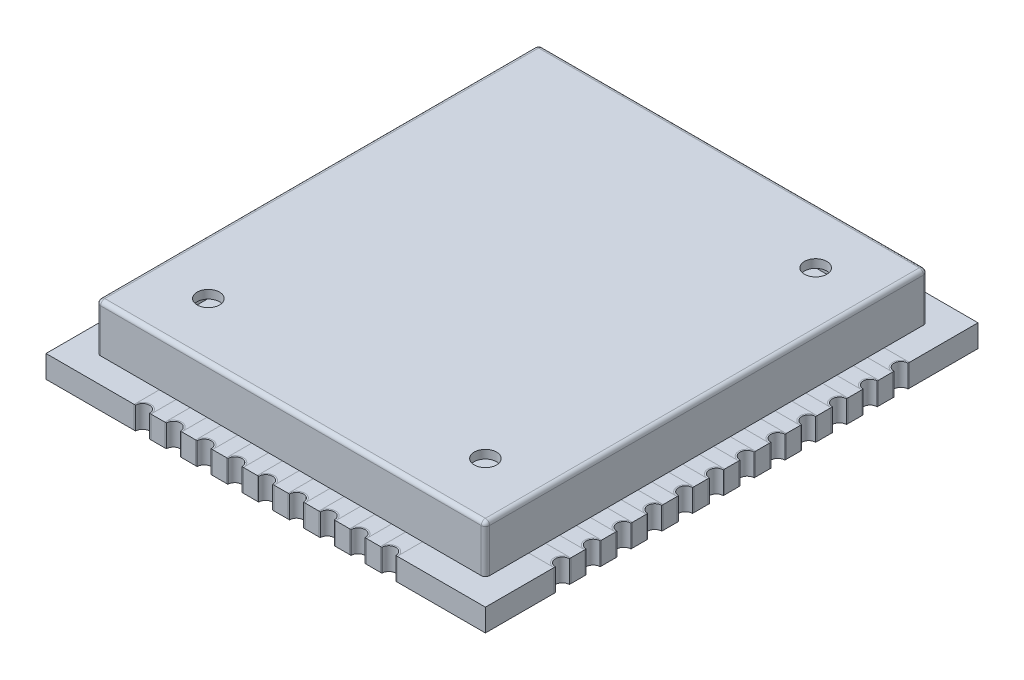
SolidWorks part; units mm, degrees
note: The reader was unsure of these and kept them because the rebuilt part matched: shared geometry of "Sketch5<2>", "Sketch5<3>", "Sketch5<4>", "Sketch3<2>".
other "Shield"
other "PCB"
ref_plane "Front Plane" through (0, 0, 0) normal (0, 0, 1) x (1, 0, 0)
ref_plane "Top Plane" through (0, 0, 0) normal (0, 1, 0) x (1, 0, 0)
ref_plane "Right Plane" through (0, 0, 0) normal (1, 0, 0) x (0, 0, -1)
sketch "Sketch1" plane through (0, 0, 0) normal (0, 1, 0) x (1, 0, 0)
  line L1 (-7.85, -8.8) -> (7.85, -8.8)
  line L2 (-7.85, -8.8) -> (-7.85, 8.8)
  line L3 (-7.85, 8.8) -> (7.85, 8.8)
  line L4 (7.85, -8.8) -> (7.85, 8.8)
  line L5 (-7.85, -8.8) -> (7.85, 8.8) construction
  line L6 (-7.85, 8.8) -> (7.85, -8.8) construction
  point P0 (0, 0)
  dimension "D1" = 17.6
  dimension "D2" = 15.7
extrude "PCB BASE" add sketch "Sketch1" along normal blind 0.8
sketch "Sketch2" plane through (0, 0, 0) normal (0, 1, 0) x (1, 0, 0)
  line L1 (-6.95, -7.9) -> (6.95, -7.9)
  line L2 (-6.95, -7.9) -> (-6.95, 7.9)
  line L3 (-6.95, 7.9) -> (6.95, 7.9)
  line L4 (6.95, -7.9) -> (6.95, 7.9)
  line L5 (-6.95, -7.9) -> (6.95, 7.9) construction
  line L6 (-6.95, 7.9) -> (6.95, -7.9) construction
  point P0 (0, 0)
  dimension "D1" = 15.8
  dimension "D2" = 13.9
extrude "SHIELD" add sketch "Sketch2" along normal blind 1.7 from surface at 0.8 separate body starting at face at (0, 0.8, 0)
shell "Shield shelling" thickness 0.3
sketch "Sketch4" plane through (0, 0, 0) normal (0, 1, 0) x (1, 0, 0)
  line L0 (-6.95, 7.9) -> (-6.95, -7.9) construction
  line L1 (-6.95, -7.9) -> (6.95, -7.9) construction
  line L2 (6.95, -7.9) -> (6.95, 7.9) construction
  line L3 (6.95, 7.9) -> (-6.95, 7.9) construction
  circle A0 centre (-4.95, -5.9) radius 0.4
  circle A1 centre (4.95, 5.9) radius 0.4
  circle A2 centre (4.95, -5.9) radius 0.4
  dimension "D1" = 0.8
  dimension "D2" = 0.8
  dimension "D3" = 0.8
  dimension "D4" = 2
  dimension "D5" = 2
  dimension "D6" = 2
  dimension "D7" = 2
extrude "Holes in shield" cut sketch "Sketch4" against normal up to next from surface
sketch "Sketch3" plane through (0, 0, 0) normal (0, 1, 0) x (1, 0, 0)
  line L0 (-7.85, 8.8) -> (-7.85, -8.8) construction
  line L1 (-7.85, -8.8) -> (7.85, -8.8) construction
  line L2 (-7.85, -5.75) -> (-7.85, -6.35)
  line L3 (-7.85, -4.65) -> (-7.85, -5.25)
  line L4 (-7.85, -3.55) -> (-7.85, -4.15)
  line L5 (-7.85, -2.45) -> (-7.85, -3.05)
  line L6 (-7.85, -1.35) -> (-7.85, -1.95)
  line L7 (-7.85, -0.25) -> (-7.85, -0.85)
  line L8 (-7.85, 0.85) -> (-7.85, 0.25)
  line L9 (-7.85, 1.95) -> (-7.85, 1.35)
  line L10 (-7.85, 3.05) -> (-7.85, 2.45)
  line L11 (-7.85, 4.15) -> (-7.85, 3.55)
  line L12 (-7.85, 5.25) -> (-7.85, 4.65)
  line L13 (-7.85, 6.35) -> (-7.85, 5.75)
  line L14 (0, 8.8) -> (0, -8.8) construction
  line L15 (7.85, 8.8) -> (-7.85, 8.8) construction
  line L16 (7.85, 6.35) -> (7.85, 5.75)
  line L17 (7.85, 5.25) -> (7.85, 4.65)
  line L18 (7.85, 4.15) -> (7.85, 3.55)
  line L19 (7.85, 3.05) -> (7.85, 2.45)
  line L20 (7.85, 1.95) -> (7.85, 1.35)
  line L21 (7.85, 0.85) -> (7.85, 0.25)
  line L22 (7.85, -0.25) -> (7.85, -0.85)
  line L23 (7.85, -1.35) -> (7.85, -1.95)
  line L24 (7.85, -2.45) -> (7.85, -3.05)
  line L25 (7.85, -3.55) -> (7.85, -4.15)
  line L26 (7.85, -4.65) -> (7.85, -5.25)
  line L27 (7.85, -5.75) -> (7.85, -6.35)
  line L28 (-4.7, -8.8) -> (-4.1, -8.8)
  line L29 (-3.6, -8.8) -> (-3, -8.8)
  line L30 (-2.5, -8.8) -> (-1.9, -8.8)
  line L31 (-1.4, -8.8) -> (-0.8, -8.8)
  line L32 (-0.3, -8.8) -> (0.3, -8.8)
  line L33 (0.8, -8.8) -> (1.4, -8.8)
  line L34 (1.9, -8.8) -> (2.5, -8.8)
  line L35 (3, -8.8) -> (3.6, -8.8)
  line L36 (4.1, -8.8) -> (4.7, -8.8)
  line L37 (-7.85, 0) -> (7.85, 0) construction
  line L38 (7.85, -8.8) -> (7.85, 8.8) construction
  line L39 (4.1, 8.8) -> (4.7, 8.8)
  line L40 (3, 8.8) -> (3.6, 8.8)
  line L41 (1.9, 8.8) -> (2.5, 8.8)
  line L42 (0.8, 8.8) -> (1.4, 8.8)
  line L43 (-0.3, 8.8) -> (0.3, 8.8)
  line L44 (-1.4, 8.8) -> (-0.8, 8.8)
  line L45 (-2.5, 8.8) -> (-1.9, 8.8)
  line L46 (-3.6, 8.8) -> (-3, 8.8)
  line L47 (-4.7, 8.8) -> (-4.1, 8.8)
  arc A0 (-7.85, -5.75) -> (-7.85, -6.35) centre (-7.85, -6.05) cw
  arc A1 (-7.85, -4.65) -> (-7.85, -5.25) centre (-7.85, -4.95) cw
  arc A2 (-7.85, -3.55) -> (-7.85, -4.15) centre (-7.85, -3.85) cw
  arc A3 (-7.85, -2.45) -> (-7.85, -3.05) centre (-7.85, -2.75) cw
  arc A4 (-7.85, -1.35) -> (-7.85, -1.95) centre (-7.85, -1.65) cw
  arc A5 (-7.85, -0.25) -> (-7.85, -0.85) centre (-7.85, -0.55) cw
  arc A6 (-7.85, 0.85) -> (-7.85, 0.25) centre (-7.85, 0.55) cw
  arc A7 (-7.85, 1.95) -> (-7.85, 1.35) centre (-7.85, 1.65) cw
  arc A8 (-7.85, 3.05) -> (-7.85, 2.45) centre (-7.85, 2.75) cw
  arc A9 (-7.85, 4.15) -> (-7.85, 3.55) centre (-7.85, 3.85) cw
  arc A10 (-7.85, 5.25) -> (-7.85, 4.65) centre (-7.85, 4.95) cw
  arc A11 (-7.85, 6.35) -> (-7.85, 5.75) centre (-7.85, 6.05) cw
  arc A12 (7.85, 6.35) -> (7.85, 5.75) centre (7.85, 6.05) ccw
  arc A13 (7.85, 5.25) -> (7.85, 4.65) centre (7.85, 4.95) ccw
  arc A14 (7.85, 4.15) -> (7.85, 3.55) centre (7.85, 3.85) ccw
  arc A15 (7.85, 3.05) -> (7.85, 2.45) centre (7.85, 2.75) ccw
  arc A16 (7.85, 1.95) -> (7.85, 1.35) centre (7.85, 1.65) ccw
  arc A17 (7.85, 0.85) -> (7.85, 0.25) centre (7.85, 0.55) ccw
  arc A18 (7.85, -0.25) -> (7.85, -0.85) centre (7.85, -0.55) ccw
  arc A19 (7.85, -1.35) -> (7.85, -1.95) centre (7.85, -1.65) ccw
  arc A20 (7.85, -2.45) -> (7.85, -3.05) centre (7.85, -2.75) ccw
  arc A21 (7.85, -3.55) -> (7.85, -4.15) centre (7.85, -3.85) ccw
  arc A22 (7.85, -4.65) -> (7.85, -5.25) centre (7.85, -4.95) ccw
  arc A23 (7.85, -5.75) -> (7.85, -6.35) centre (7.85, -6.05) ccw
  arc A24 (-4.7, -8.8) -> (-4.1, -8.8) centre (-4.4, -8.8) cw
  arc A25 (-3.6, -8.8) -> (-3, -8.8) centre (-3.3, -8.8) cw
  arc A26 (-2.5, -8.8) -> (-1.9, -8.8) centre (-2.2, -8.8) cw
  arc A27 (-1.4, -8.8) -> (-0.8, -8.8) centre (-1.1, -8.8) cw
  arc A28 (-0.3, -8.8) -> (0.3, -8.8) centre (0, -8.8) cw
  arc A29 (0.8, -8.8) -> (1.4, -8.8) centre (1.1, -8.8) cw
  arc A30 (1.9, -8.8) -> (2.5, -8.8) centre (2.2, -8.8) cw
  arc A31 (3, -8.8) -> (3.6, -8.8) centre (3.3, -8.8) cw
  arc A32 (4.1, -8.8) -> (4.7, -8.8) centre (4.4, -8.8) cw
  arc A33 (4.1, 8.8) -> (4.7, 8.8) centre (4.4, 8.8) ccw
  arc A34 (3, 8.8) -> (3.6, 8.8) centre (3.3, 8.8) ccw
  arc A35 (1.9, 8.8) -> (2.5, 8.8) centre (2.2, 8.8) ccw
  arc A36 (0.8, 8.8) -> (1.4, 8.8) centre (1.1, 8.8) ccw
  arc A37 (-0.3, 8.8) -> (0.3, 8.8) centre (0, 8.8) ccw
  arc A38 (-1.4, 8.8) -> (-0.8, 8.8) centre (-1.1, 8.8) ccw
  arc A39 (-2.5, 8.8) -> (-1.9, 8.8) centre (-2.2, 8.8) ccw
  arc A40 (-3.6, 8.8) -> (-3, 8.8) centre (-3.3, 8.8) ccw
  arc A41 (-4.7, 8.8) -> (-4.1, 8.8) centre (-4.4, 8.8) ccw
  point P0 (-7.85, -6.05)
  dimension "D2" = 0.3
  dimension "D4" = 0.3
  dimension "D1" = 2.75
  dimension "D5" = 3.45
  dimension "D3" = 12
  dimension "D6" = 9
extrude "Cut-Extrude1" cut sketch "Sketch3" against normal through all and the other way through all
sketch "Sketch5" plane through (0, 0, 0) normal (0, 1, 0) x (1, 0, 0)
  line L0 (-7.85, -4.65) -> (-6.85, -4.65)
  line L1 (-7.85, -5.75) -> (-6.85, -5.75)
  line L2 (-7.85, -5.75) -> (-7.85, -6.35)
  line L3 (-7.85, -6.35) -> (-6.85, -6.35)
  line L4 (-6.85, -5.75) -> (-6.85, -6.35)
  line L5 (-7.85, -4.65) -> (-7.85, -5.25)
  line L6 (-7.85, -5.25) -> (-6.85, -5.25)
  line L7 (-6.85, -4.65) -> (-6.85, -5.25)
  line L8 (-7.85, -3.55) -> (-6.85, -3.55)
  line L9 (-7.85, -3.55) -> (-7.85, -4.15)
  line L10 (-7.85, -4.15) -> (-6.85, -4.15)
  line L11 (-6.85, -3.55) -> (-6.85, -4.15)
  line L12 (-7.85, -2.45) -> (-6.85, -2.45)
  line L13 (-7.85, -2.45) -> (-7.85, -3.05)
  line L14 (-7.85, -3.05) -> (-6.85, -3.05)
  line L15 (-6.85, -2.45) -> (-6.85, -3.05)
  line L16 (-7.85, -1.35) -> (-6.85, -1.35)
  line L17 (-7.85, -1.35) -> (-7.85, -1.95)
  line L18 (-7.85, -1.95) -> (-6.85, -1.95)
  line L19 (-6.85, -1.35) -> (-6.85, -1.95)
  line L20 (-7.85, -0.25) -> (-6.85, -0.25)
  line L21 (-7.85, -0.25) -> (-7.85, -0.85)
  line L22 (-7.85, -0.85) -> (-6.85, -0.85)
  line L23 (-6.85, -0.25) -> (-6.85, -0.85)
  line L24 (-7.85, 0.85) -> (-6.85, 0.85)
  line L25 (-7.85, 0.85) -> (-7.85, 0.25)
  line L26 (-7.85, 0.25) -> (-6.85, 0.25)
  line L27 (-6.85, 0.85) -> (-6.85, 0.25)
  line L28 (-7.85, 1.95) -> (-6.85, 1.95)
  line L29 (-7.85, 1.95) -> (-7.85, 1.35)
  line L30 (-7.85, 1.35) -> (-6.85, 1.35)
  line L31 (-6.85, 1.95) -> (-6.85, 1.35)
  line L32 (-7.85, 3.05) -> (-6.85, 3.05)
  line L33 (-7.85, 3.05) -> (-7.85, 2.45)
  line L34 (-7.85, 2.45) -> (-6.85, 2.45)
  line L35 (-6.85, 3.05) -> (-6.85, 2.45)
  line L36 (-7.85, 4.15) -> (-6.85, 4.15)
  line L37 (-7.85, 4.15) -> (-7.85, 3.55)
  line L38 (-7.85, 3.55) -> (-6.85, 3.55)
  line L39 (-6.85, 4.15) -> (-6.85, 3.55)
  line L40 (-7.85, 5.25) -> (-6.85, 5.25)
  line L41 (-7.85, 5.25) -> (-7.85, 4.65)
  line L42 (-7.85, 4.65) -> (-6.85, 4.65)
  line L43 (-6.85, 5.25) -> (-6.85, 4.65)
  line L44 (-7.85, 6.35) -> (-6.85, 6.35)
  line L45 (-7.85, 6.35) -> (-7.85, 5.75)
  line L46 (-7.85, 5.75) -> (-6.85, 5.75)
  line L47 (-6.85, 6.35) -> (-6.85, 5.75)
  line L48 (-7.85, 0) -> (7.85, 0) construction
  line L49 (-7.85, 0.25) -> (-7.85, -0.25) construction
  line L50 (7.85, -0.25) -> (7.85, 0.25) construction
  line L51 (0, 8.5) -> (0, -8.5) construction
  line L52 (7.85, 5.25) -> (6.85, 5.25) [skipped]
  line L53 (7.85, 6.35) -> (6.85, 6.35)
  line L54 (7.85, 6.35) -> (7.85, 5.75)
  line L55 (7.85, 5.75) -> (6.85, 5.75)
  line L56 (6.85, 6.35) -> (6.85, 5.75)
  line L57 (7.85, 5.25) -> (7.85, 4.65) [skipped]
  line L58 (7.85, 4.65) -> (6.85, 4.65) [skipped]
  line L59 (6.85, 5.25) -> (6.85, 4.65) [skipped]
  line L60 (7.85, 4.15) -> (6.85, 4.15)
  line L61 (7.85, 4.15) -> (7.85, 3.55)
  line L62 (7.85, 3.55) -> (6.85, 3.55)
  line L63 (6.85, 4.15) -> (6.85, 3.55)
  line L64 (7.85, 3.05) -> (6.85, 3.05)
  line L65 (7.85, 3.05) -> (7.85, 2.45)
  line L66 (7.85, 2.45) -> (6.85, 2.45)
  line L67 (6.85, 3.05) -> (6.85, 2.45)
  line L68 (6.85, 1.95) -> (6.85, 1.35)
  line L69 (7.85, 1.35) -> (6.85, 1.35)
  line L70 (7.85, 1.95) -> (7.85, 1.35)
  line L71 (7.85, 1.95) -> (6.85, 1.95)
  line L72 (6.85, 0.85) -> (6.85, 0.25)
  line L73 (7.85, 0.25) -> (6.85, 0.25)
  line L74 (7.85, 0.85) -> (7.85, 0.25)
  line L75 (7.85, 0.85) -> (6.85, 0.85)
  line L76 (6.85, -0.25) -> (6.85, -0.85)
  line L77 (7.85, -0.85) -> (6.85, -0.85)
  line L78 (7.85, -0.25) -> (7.85, -0.85)
  line L79 (7.85, -0.25) -> (6.85, -0.25)
  line L80 (6.85, -1.35) -> (6.85, -1.95)
  line L81 (7.85, -1.95) -> (6.85, -1.95)
  line L82 (7.85, -1.35) -> (7.85, -1.95)
  line L83 (7.85, -1.35) -> (6.85, -1.35)
  line L84 (6.85, -2.45) -> (6.85, -3.05)
  line L85 (7.85, -3.05) -> (6.85, -3.05)
  line L86 (7.85, -2.45) -> (7.85, -3.05)
  line L87 (7.85, -2.45) -> (6.85, -2.45)
  line L88 (6.85, -3.55) -> (6.85, -4.15)
  line L89 (7.85, -4.15) -> (6.85, -4.15)
  line L90 (7.85, -3.55) -> (7.85, -4.15)
  line L91 (7.85, -3.55) -> (6.85, -3.55)
  line L92 (6.85, -4.65) -> (6.85, -5.25)
  line L93 (7.85, -5.25) -> (6.85, -5.25)
  line L94 (7.85, -4.65) -> (7.85, -5.25)
  line L95 (6.85, -5.75) -> (6.85, -6.35)
  line L96 (7.85, -6.35) -> (6.85, -6.35)
  line L97 (7.85, -5.75) -> (7.85, -6.35)
  line L98 (7.85, -5.75) -> (6.85, -5.75)
  line L99 (7.85, -4.65) -> (6.85, -4.65)
  line L100 (-3.6, -8.8) -> (-3, -8.8)
  line L101 (-4.7, -8.8) -> (-4.1, -8.8)
  line L102 (-4.7, -8.8) -> (-4.7, -7.8)
  line L103 (-4.7, -7.8) -> (-4.1, -7.8)
  line L104 (-4.1, -8.8) -> (-4.1, -7.8)
  line L105 (-3.6, -8.8) -> (-3.6, -7.8)
  line L106 (-3.6, -7.8) -> (-3, -7.8)
  line L107 (-3, -8.8) -> (-3, -7.8)
  line L108 (-2.5, -8.8) -> (-1.9, -8.8)
  line L109 (-2.5, -8.8) -> (-2.5, -7.8)
  line L110 (-2.5, -7.8) -> (-1.9, -7.8)
  line L111 (-1.9, -8.8) -> (-1.9, -7.8)
  line L112 (-1.4, -8.8) -> (-0.8, -8.8)
  line L113 (-1.4, -8.8) -> (-1.4, -7.8)
  line L114 (-1.4, -7.8) -> (-0.8, -7.8)
  line L115 (-0.8, -8.8) -> (-0.8, -7.8)
  line L116 (-0.3, -8.8) -> (0.3, -8.8)
  line L117 (-0.3, -8.8) -> (-0.3, -7.8)
  line L118 (-0.3, -7.8) -> (0.3, -7.8)
  line L119 (0.3, -8.8) -> (0.3, -7.8)
  line L120 (0.8, -8.8) -> (1.4, -8.8)
  line L121 (0.8, -8.8) -> (0.8, -7.8)
  line L122 (0.8, -7.8) -> (1.4, -7.8)
  line L123 (1.4, -8.8) -> (1.4, -7.8)
  line L124 (1.9, -8.8) -> (2.5, -8.8)
  line L125 (1.9, -8.8) -> (1.9, -7.8)
  line L126 (1.9, -7.8) -> (2.5, -7.8)
  line L127 (2.5, -8.8) -> (2.5, -7.8)
  line L128 (3, -8.8) -> (3.6, -8.8)
  line L129 (3, -8.8) -> (3, -7.8)
  line L130 (3, -7.8) -> (3.6, -7.8)
  line L131 (3.6, -8.8) -> (3.6, -7.8)
  line L132 (4.1, -8.8) -> (4.7, -8.8)
  line L133 (4.1, -8.8) -> (4.1, -7.8)
  line L134 (4.1, -7.8) -> (4.7, -7.8)
  line L135 (4.7, -8.8) -> (4.7, -7.8)
  line L136 (4.7, 8.8) -> (4.7, 7.8)
  line L137 (4.1, 7.8) -> (4.7, 7.8)
  line L138 (4.1, 8.8) -> (4.1, 7.8)
  line L139 (4.1, 8.8) -> (4.7, 8.8)
  line L140 (3.6, 8.8) -> (3.6, 7.8)
  line L141 (3, 7.8) -> (3.6, 7.8)
  line L142 (3, 8.8) -> (3, 7.8)
  line L143 (3, 8.8) -> (3.6, 8.8)
  line L144 (2.5, 8.8) -> (2.5, 7.8)
  line L145 (1.9, 7.8) -> (2.5, 7.8)
  line L146 (1.9, 8.8) -> (1.9, 7.8)
  line L147 (1.9, 8.8) -> (2.5, 8.8)
  line L148 (1.4, 8.8) -> (1.4, 7.8)
  line L149 (0.8, 7.8) -> (1.4, 7.8)
  line L150 (0.8, 8.8) -> (0.8, 7.8)
  line L151 (0.8, 8.8) -> (1.4, 8.8)
  line L152 (0.3, 8.8) -> (0.3, 7.8)
  line L153 (-0.3, 7.8) -> (0.3, 7.8)
  line L154 (-0.3, 8.8) -> (-0.3, 7.8)
  line L155 (-0.3, 8.8) -> (0.3, 8.8)
  line L156 (-0.8, 8.8) -> (-0.8, 7.8)
  line L157 (-1.4, 7.8) -> (-0.8, 7.8)
  line L158 (-1.4, 8.8) -> (-1.4, 7.8)
  line L159 (-1.4, 8.8) -> (-0.8, 8.8)
  line L160 (-1.9, 8.8) -> (-1.9, 7.8)
  line L161 (-2.5, 7.8) -> (-1.9, 7.8)
  line L162 (-2.5, 8.8) -> (-2.5, 7.8)
  line L163 (-2.5, 8.8) -> (-1.9, 8.8)
  line L164 (-3, 8.8) -> (-3, 7.8)
  line L165 (-3.6, 7.8) -> (-3, 7.8)
  line L166 (-3.6, 8.8) -> (-3.6, 7.8)
  line L167 (-4.1, 8.8) -> (-4.1, 7.8)
  line L168 (-4.7, 7.8) -> (-4.1, 7.8)
  line L169 (-4.7, 8.8) -> (-4.7, 7.8)
  line L170 (-4.7, 8.8) -> (-4.1, 8.8)
  line L171 (-3.6, 8.8) -> (-3, 8.8)
  line L387 (7.85, 5.25) -> (6.85, 5.25)
  line L388 (7.85, 5.25) -> (7.85, 4.65)
  line L389 (7.85, 4.65) -> (6.85, 4.65)
  line L390 (6.85, 5.25) -> (6.85, 4.65)
  arc A0 (-0.3, 8.8) -> (0.3, 8.8) centre (0, 8.8) ccw construction
  arc A1 (0.3, -8.8) -> (-0.3, -8.8) centre (0, -8.8) ccw construction
  point P186 (6.85, 6.35)
  dimension "D1" = 1
  dimension "D3" = 1
  dimension "D2" = 12
  dimension "D4" = 9
  dimension "D28" = 4
extrude "Cut-Extrude5" cut sketch "Sketch5" along normal blind 0.05
extrude "Cut-Extrude7" cut sketch "Sketch5<2>" against normal blind 0.05 from offset 0.8
sketch "Sketch5<2>" plane through (0, 0, 0) normal (0, 1, 0) x (1, 0, 0) same geometry as "Sketch5"
extrude "Boss-Extrude3" add sketch "Sketch5<3>" along normal blind 0.05 separate body
sketch "Sketch5<3>" plane through (0, 0, 0) normal (0, 1, 0) x (1, 0, 0) same geometry as "Sketch5"
extrude "Boss-Extrude4" add sketch "Sketch5<4>" against normal blind 0.05 from offset 0.8 separate body
sketch "Sketch5<4>" plane through (0, 0, 0) normal (0, 1, 0) x (1, 0, 0) same geometry as "Sketch5"
extrude "Cut-Extrude8" cut sketch "Sketch3<2>" against normal through all and the other way through all
sketch "Sketch3<2>" plane through (0, 0, 0) normal (0, 1, 0) x (1, 0, 0) same geometry as "Sketch3"
sketch "Sketch6" plane through (0, 0, 0) normal (0, 1, 0) x (1, 0, 0)
  line L2 (-7.85, -5.75) -> (-7.85, -5.8)
  line L3 (-4.7, -8.8) -> (-4.65, -8.8)
  line L4 (-4.1, -8.8) -> (-4.15, -8.8)
  line L5 (-3.6, -8.8) -> (-3.55, -8.8)
  line L6 (-3, -8.8) -> (-3.05, -8.8)
  line L7 (-2.5, -8.8) -> (-2.45, -8.8)
  line L8 (-1.9, -8.8) -> (-1.95, -8.8)
  line L9 (-1.4, -8.8) -> (-1.35, -8.8)
  line L10 (-0.8, -8.8) -> (-0.85, -8.8)
  line L11 (-0.3, -8.8) -> (-0.25, -8.8)
  line L12 (0.3, -8.8) -> (0.25, -8.8)
  line L13 (0.8, -8.8) -> (0.85, -8.8)
  line L14 (0, 8.8) -> (0, -8.8) construction
  line L16 (7.85, -5.75) -> (7.85, -5.8)
  line L17 (7.85, -6.35) -> (7.85, -6.3)
  line L18 (7.85, -4.65) -> (7.85, -4.7)
  line L19 (7.85, -5.25) -> (7.85, -5.2)
  line L20 (7.85, -3.55) -> (7.85, -3.6)
  line L21 (7.85, -4.15) -> (7.85, -4.1)
  line L22 (7.85, -2.45) -> (7.85, -2.5)
  line L23 (7.85, -3.05) -> (7.85, -3)
  line L24 (7.85, -1.35) -> (7.85, -1.4)
  line L25 (7.85, -1.95) -> (7.85, -1.9)
  line L26 (7.85, -0.25) -> (7.85, -0.3)
  line L27 (7.85, -0.85) -> (7.85, -0.8)
  line L28 (1.4, -8.8) -> (1.35, -8.8)
  line L29 (1.9, -8.8) -> (1.95, -8.8)
  line L30 (2.5, -8.8) -> (2.45, -8.8)
  line L31 (3, -8.8) -> (3.05, -8.8)
  line L32 (3.6, -8.8) -> (3.55, -8.8)
  line L33 (4.1, -8.8) -> (4.15, -8.8)
  line L34 (4.7, -8.8) -> (4.65, -8.8)
  line L35 (7.85, 0.85) -> (7.85, 0.8)
  line L36 (7.85, 0.25) -> (7.85, 0.3)
  line L37 (-7.85, 0) -> (7.85, 0) construction
  line L39 (-4.7, 8.8) -> (-4.65, 8.8)
  line L40 (-4.1, 8.8) -> (-4.15, 8.8)
  line L41 (-3.6, 8.8) -> (-3.55, 8.8)
  line L42 (-3, 8.8) -> (-3.05, 8.8)
  line L43 (-2.5, 8.8) -> (-2.45, 8.8)
  line L44 (-1.9, 8.8) -> (-1.95, 8.8)
  line L45 (-1.4, 8.8) -> (-1.35, 8.8)
  line L46 (-0.8, 8.8) -> (-0.85, 8.8)
  line L47 (-0.3, 8.8) -> (-0.25, 8.8)
  line L48 (-7.85, -6.35) -> (-7.85, -6.3)
  line L49 (-7.85, -4.65) -> (-7.85, -4.7)
  line L50 (-7.85, -5.25) -> (-7.85, -5.2)
  line L51 (-7.85, -3.55) -> (-7.85, -3.6)
  line L52 (-7.85, -4.15) -> (-7.85, -4.1)
  line L53 (-7.85, -2.45) -> (-7.85, -2.5)
  line L54 (-7.85, -3.05) -> (-7.85, -3)
  line L55 (-7.85, -1.35) -> (-7.85, -1.4)
  line L56 (-7.85, -1.95) -> (-7.85, -1.9)
  line L57 (-7.85, -0.25) -> (-7.85, -0.3)
  line L58 (-7.85, -0.85) -> (-7.85, -0.8)
  line L59 (-7.85, 0.85) -> (-7.85, 0.8)
  line L60 (-7.85, 0.25) -> (-7.85, 0.3)
  line L61 (-7.85, 1.95) -> (-7.85, 1.9)
  line L62 (-7.85, 1.35) -> (-7.85, 1.4)
  line L63 (-7.85, 3.05) -> (-7.85, 3)
  line L64 (-7.85, 2.45) -> (-7.85, 2.5)
  line L65 (-7.85, 4.15) -> (-7.85, 4.1)
  line L66 (-7.85, 3.55) -> (-7.85, 3.6)
  line L67 (-7.85, 5.25) -> (-7.85, 5.2)
  line L68 (-7.85, 4.65) -> (-7.85, 4.7)
  line L69 (-7.85, 6.35) -> (-7.85, 6.3)
  line L70 (-7.85, 5.75) -> (-7.85, 5.8)
  line L71 (7.85, 1.95) -> (7.85, 1.9)
  line L72 (7.85, 1.35) -> (7.85, 1.4)
  line L73 (7.85, 3.05) -> (7.85, 3)
  line L74 (7.85, 2.45) -> (7.85, 2.5)
  line L75 (7.85, 4.15) -> (7.85, 4.1)
  line L76 (7.85, 3.55) -> (7.85, 3.6)
  line L77 (7.85, 5.25) -> (7.85, 5.2)
  line L78 (7.85, 4.65) -> (7.85, 4.7)
  line L79 (7.85, 6.35) -> (7.85, 6.3)
  line L80 (7.85, 5.75) -> (7.85, 5.8)
  line L81 (0.3, 8.8) -> (0.25, 8.8)
  line L82 (0.8, 8.8) -> (0.85, 8.8)
  line L83 (1.4, 8.8) -> (1.35, 8.8)
  line L84 (1.9, 8.8) -> (1.95, 8.8)
  line L85 (2.5, 8.8) -> (2.45, 8.8)
  line L86 (3, 8.8) -> (3.05, 8.8)
  line L87 (3.6, 8.8) -> (3.55, 8.8)
  line L88 (4.1, 8.8) -> (4.15, 8.8)
  line L89 (4.7, 8.8) -> (4.65, 8.8)
  arc A0 (-7.85, -5.75) -> (-7.85, -6.35) centre (-7.85, -6.05) cw
  arc A1 (-7.85, -4.65) -> (-7.85, -5.25) centre (-7.85, -4.95) cw
  arc A2 (-7.85, -3.55) -> (-7.85, -4.15) centre (-7.85, -3.85) cw
  arc A3 (-7.85, -2.45) -> (-7.85, -3.05) centre (-7.85, -2.75) cw
  arc A4 (-7.85, -1.35) -> (-7.85, -1.95) centre (-7.85, -1.65) cw
  arc A5 (-7.85, -0.25) -> (-7.85, -0.85) centre (-7.85, -0.55) cw
  arc A6 (-7.85, 0.85) -> (-7.85, 0.25) centre (-7.85, 0.55) cw
  arc A7 (-7.85, 1.95) -> (-7.85, 1.35) centre (-7.85, 1.65) cw
  arc A8 (-7.85, 3.05) -> (-7.85, 2.45) centre (-7.85, 2.75) cw
  arc A9 (-7.85, 4.15) -> (-7.85, 3.55) centre (-7.85, 3.85) cw
  arc A10 (-7.85, 5.25) -> (-7.85, 4.65) centre (-7.85, 4.95) cw
  arc A11 (-7.85, 6.35) -> (-7.85, 5.75) centre (-7.85, 6.05) cw
  arc A12 (7.85, 6.35) -> (7.85, 5.75) centre (7.85, 6.05) ccw
  arc A13 (7.85, 5.25) -> (7.85, 4.65) centre (7.85, 4.95) ccw
  arc A14 (7.85, 4.15) -> (7.85, 3.55) centre (7.85, 3.85) ccw
  arc A15 (7.85, 3.05) -> (7.85, 2.45) centre (7.85, 2.75) ccw
  arc A16 (7.85, 1.95) -> (7.85, 1.35) centre (7.85, 1.65) ccw
  arc A17 (7.85, 0.85) -> (7.85, 0.25) centre (7.85, 0.55) ccw
  arc A18 (7.85, -0.25) -> (7.85, -0.85) centre (7.85, -0.55) ccw
  arc A19 (7.85, -1.35) -> (7.85, -1.95) centre (7.85, -1.65) ccw
  arc A20 (7.85, -2.45) -> (7.85, -3.05) centre (7.85, -2.75) ccw
  arc A21 (7.85, -3.55) -> (7.85, -4.15) centre (7.85, -3.85) ccw
  arc A22 (7.85, -4.65) -> (7.85, -5.25) centre (7.85, -4.95) ccw
  arc A23 (7.85, -5.75) -> (7.85, -6.35) centre (7.85, -6.05) ccw
  arc A24 (-4.7, -8.8) -> (-4.1, -8.8) centre (-4.4, -8.8) cw
  arc A25 (-3.6, -8.8) -> (-3, -8.8) centre (-3.3, -8.8) cw
  arc A26 (-2.5, -8.8) -> (-1.9, -8.8) centre (-2.2, -8.8) cw
  arc A27 (-1.4, -8.8) -> (-0.8, -8.8) centre (-1.1, -8.8) cw
  arc A28 (-0.3, -8.8) -> (0.3, -8.8) centre (0, -8.8) cw
  arc A29 (0.8, -8.8) -> (1.4, -8.8) centre (1.1, -8.8) cw
  arc A30 (1.9, -8.8) -> (2.5, -8.8) centre (2.2, -8.8) cw
  arc A31 (3, -8.8) -> (3.6, -8.8) centre (3.3, -8.8) cw
  arc A32 (4.1, -8.8) -> (4.7, -8.8) centre (4.4, -8.8) cw
  arc A33 (4.1, 8.8) -> (4.7, 8.8) centre (4.4, 8.8) ccw
  arc A34 (3, 8.8) -> (3.6, 8.8) centre (3.3, 8.8) ccw
  arc A35 (1.9, 8.8) -> (2.5, 8.8) centre (2.2, 8.8) ccw
  arc A36 (0.8, 8.8) -> (1.4, 8.8) centre (1.1, 8.8) ccw
  arc A37 (-0.3, 8.8) -> (0.3, 8.8) centre (0, 8.8) ccw
  arc A38 (-1.4, 8.8) -> (-0.8, 8.8) centre (-1.1, 8.8) ccw
  arc A39 (-2.5, 8.8) -> (-1.9, 8.8) centre (-2.2, 8.8) ccw
  arc A40 (-3.6, 8.8) -> (-3, 8.8) centre (-3.3, 8.8) ccw
  arc A41 (-4.7, 8.8) -> (-4.1, 8.8) centre (-4.4, 8.8) ccw
  arc A42 (-7.85, -5.8) -> (-7.85, -6.3) centre (-7.85, -6.05) cw
  arc A43 (-7.85, -4.7) -> (-7.85, -5.2) centre (-7.85, -4.95) cw
  arc A44 (-7.85, -3.6) -> (-7.85, -4.1) centre (-7.85, -3.85) cw
  arc A45 (-7.85, -2.5) -> (-7.85, -3) centre (-7.85, -2.75) cw
  arc A46 (-7.85, -1.4) -> (-7.85, -1.9) centre (-7.85, -1.65) cw
  arc A47 (-7.85, -0.3) -> (-7.85, -0.8) centre (-7.85, -0.55) cw
  arc A48 (-7.85, 0.8) -> (-7.85, 0.3) centre (-7.85, 0.55) cw
  arc A49 (-7.85, 1.9) -> (-7.85, 1.4) centre (-7.85, 1.65) cw
  arc A50 (-7.85, 3) -> (-7.85, 2.5) centre (-7.85, 2.75) cw
  arc A51 (-7.85, 4.1) -> (-7.85, 3.6) centre (-7.85, 3.85) cw
  arc A52 (-7.85, 5.2) -> (-7.85, 4.7) centre (-7.85, 4.95) cw
  arc A53 (-7.85, 6.3) -> (-7.85, 5.8) centre (-7.85, 6.05) cw
  arc A54 (-4.65, -8.8) -> (-4.15, -8.8) centre (-4.4, -8.8) cw
  arc A55 (-3.55, -8.8) -> (-3.05, -8.8) centre (-3.3, -8.8) cw
  arc A56 (-2.45, -8.8) -> (-1.95, -8.8) centre (-2.2, -8.8) cw
  arc A57 (-1.35, -8.8) -> (-0.85, -8.8) centre (-1.1, -8.8) cw
  arc A58 (-0.25, -8.8) -> (0.25, -8.8) centre (0, -8.8) cw
  arc A59 (0.85, -8.8) -> (1.35, -8.8) centre (1.1, -8.8) cw
  arc A60 (1.95, -8.8) -> (2.45, -8.8) centre (2.2, -8.8) cw
  arc A61 (3.05, -8.8) -> (3.55, -8.8) centre (3.3, -8.8) cw
  arc A62 (4.15, -8.8) -> (4.65, -8.8) centre (4.4, -8.8) cw
  arc A63 (7.85, -5.8) -> (7.85, -6.3) centre (7.85, -6.05) ccw
  arc A64 (7.85, -4.7) -> (7.85, -5.2) centre (7.85, -4.95) ccw
  arc A65 (7.85, -3.6) -> (7.85, -4.1) centre (7.85, -3.85) ccw
  arc A66 (7.85, -2.5) -> (7.85, -3) centre (7.85, -2.75) ccw
  arc A67 (7.85, -1.4) -> (7.85, -1.9) centre (7.85, -1.65) ccw
  arc A68 (7.85, -0.3) -> (7.85, -0.8) centre (7.85, -0.55) ccw
  arc A69 (7.85, 0.8) -> (7.85, 0.3) centre (7.85, 0.55) ccw
  arc A70 (7.85, 1.9) -> (7.85, 1.4) centre (7.85, 1.65) ccw
  arc A71 (7.85, 3) -> (7.85, 2.5) centre (7.85, 2.75) ccw
  arc A72 (7.85, 4.1) -> (7.85, 3.6) centre (7.85, 3.85) ccw
  arc A73 (7.85, 5.2) -> (7.85, 4.7) centre (7.85, 4.95) ccw
  arc A74 (7.85, 6.3) -> (7.85, 5.8) centre (7.85, 6.05) ccw
  arc A75 (-4.65, 8.8) -> (-4.15, 8.8) centre (-4.4, 8.8) ccw
  arc A76 (-3.55, 8.8) -> (-3.05, 8.8) centre (-3.3, 8.8) ccw
  arc A77 (-2.45, 8.8) -> (-1.95, 8.8) centre (-2.2, 8.8) ccw
  arc A78 (-1.35, 8.8) -> (-0.85, 8.8) centre (-1.1, 8.8) ccw
  arc A79 (-0.25, 8.8) -> (0.25, 8.8) centre (0, 8.8) ccw
  arc A80 (0.85, 8.8) -> (1.35, 8.8) centre (1.1, 8.8) ccw
  arc A81 (1.95, 8.8) -> (2.45, 8.8) centre (2.2, 8.8) ccw
  arc A82 (3.05, 8.8) -> (3.55, 8.8) centre (3.3, 8.8) ccw
  arc A83 (4.15, 8.8) -> (4.65, 8.8) centre (4.4, 8.8) ccw
  point P0 (-7.85, -6.05)
  dimension "D2" = 0.3
  dimension "D4" = 0.3
  dimension "D1" = 0.05
  dimension "D5" = 12
  dimension "D7" = 0.05
  dimension "D9" = 0.05
  dimension "D10" = 0.05
  dimension "D11" = 0.05
  dimension "D3" = 12
  dimension "D6" = 9
  dimension "D8" = 9
extrude "Boss-Extrude6" add sketch "Sketch6" along normal up to vertex (0.8 mm away) separate body up to point (-7.85, 0.8, -6.35)
fillet "Fillet1" radius 0.15 8 edges at (-6.95, 1.65, 7.9) (-6.95, 1.65, -7.9) (6.95, 1.65, 7.9) (6.95, 1.65, -7.9) (-6.95, 2.5, 0) (0, 2.5, 7.9) (0, 2.5, -7.9) (6.95, 2.5, 0)
